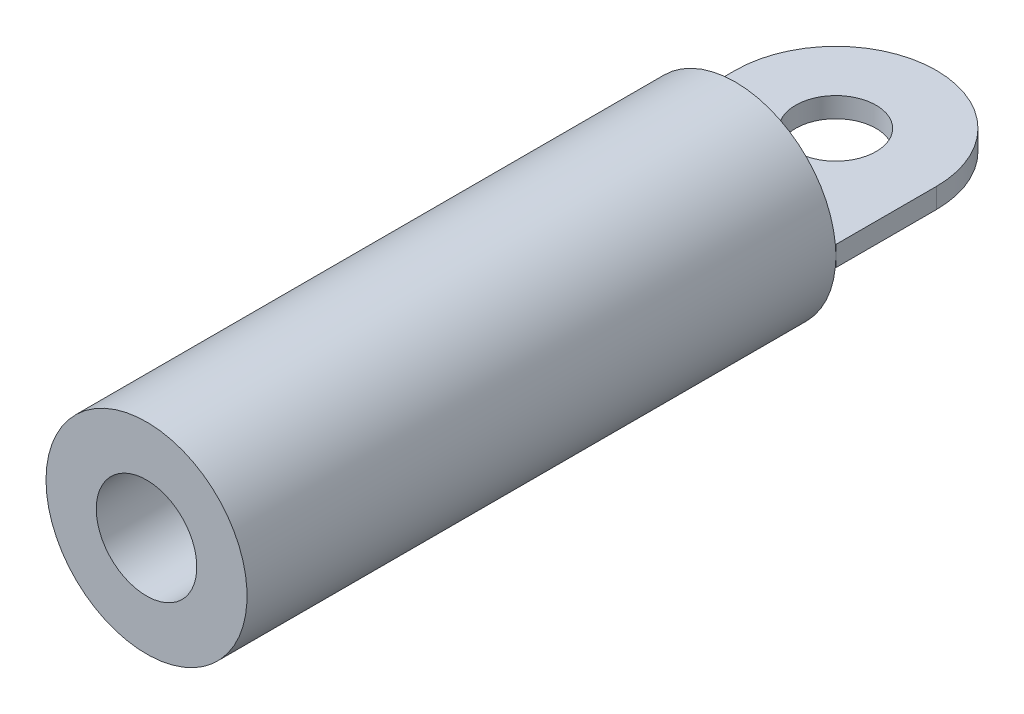
SolidWorks part; units mm, degrees
ref_plane "Front Plane" through (0, 0, 0) normal (0, 0, 1) x (1, 0, 0)
ref_plane "Top Plane" through (0, 0, 0) normal (0, 1, 0) x (1, 0, 0)
ref_plane "Right Plane" through (0, 0, 0) normal (1, 0, 0) x (0, 0, -1)
sketch "Sketch1" plane through (0, 0, 0) normal (0, 1, 0) x (1, 0, 0)
  line L0 (-1.5875, -21.7691) -> (-1.5875, -3.175)
  line L1 (-3.175, 0) -> (3.175, 0) construction
  line L2 (-3.175, 0) -> (-3.175, -21.7691)
  line L3 (-3.175, -21.7691) -> (3.175, -21.7691)
  line L4 (3.175, 0) -> (3.175, -21.7691)
  line L5 (-1.5875, -3.175) -> (1.5875, -3.175)
  line L6 (1.5875, -3.175) -> (1.5875, -21.7691)
  line L7 (-1.5875, -3.175) -> (-1.5875, 2.7496)
  line L8 (-1.5875, 2.7496) -> (1.5875, 2.7496)
  line L9 (1.5875, 2.7496) -> (1.5875, -3.175)
  line L10 (0, 0) -> (0, -50000) construction
  line L11 (0, -3.175) -> (0, 3.175)
  line L12 (-1.5875, -3.175) -> (-3.175, -3.175)
  line L13 (1.5875, -3.175) -> (3.175, -3.175)
  circle A0 centre (0, 0) radius 3.175
  arc A1 (3.175, 0) -> (-3.175, 0) centre (0, 0) ccw
  circle A2 centre (0, 0) radius 1.27
  point P9 (0, -3.175)
  dimension "D1" = 18.5941
  dimension "D2" = 6.35
  dimension "D4" = 2.54
  dimension "D3" = 3.175
revolve "Revolve6" add sketch "Sketch1" angle 360 about L10 region at (-2.3813, 0, 12.472)
extrude "Boss-Extrude1" add sketch "Sketch1<10>" along normal blind 0.3175 and the other way blind 0.3175 contours A2 L11 A0 L9 L8 | A2 L11 L8 L7 A0 | L7 A0 | L11 A0 L8 | L8 A0 L11 | L9 A0 | A0 L2 L12 L7 | A0 L7 L5 | A0 L5 L9 | A0 L9 L13 L4 region at (-1.1961, 0, 3.049) region at (-2.6086, 0, 2.4002) region at (1.1961, 0, 3.049) region at (-0.8059, 0, 3.0076) region at (0.0613, 0, 2.2225) region at (-2.2384, 0, 0) region at (2.6086, 0, 2.4002) region at (2.2384, 0, 0) region at (-0.601, 0, -2.9208) region at (0.601, 0, -2.9208)
sketch "Sketch1<10>" plane through (0, 0, 0) normal (0, 1, 0) x (1, 0, 0) same geometry as "Sketch1"
